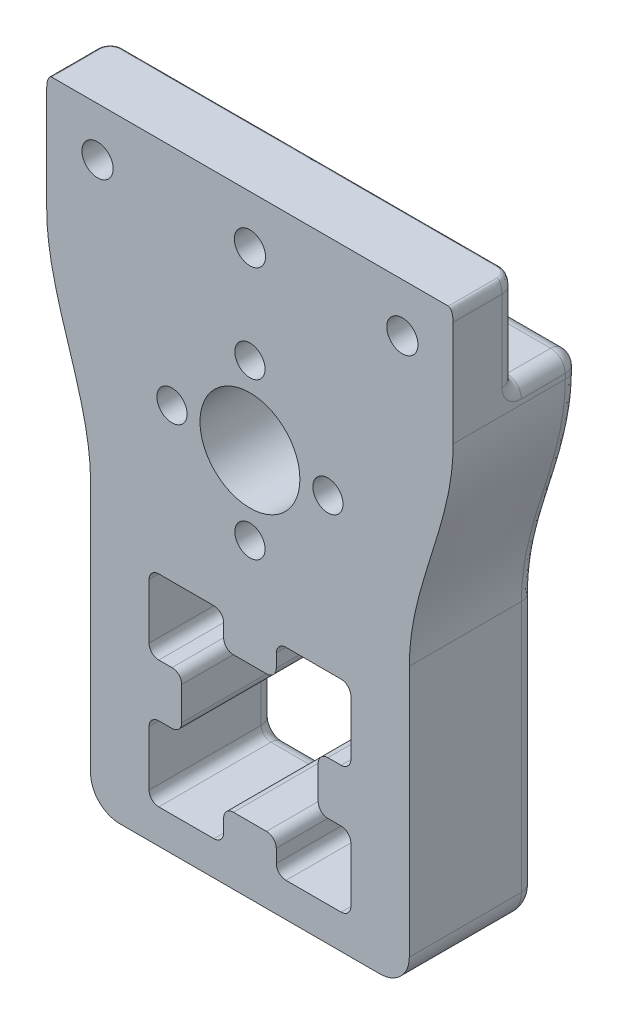
SolidWorks part; units mm, degrees
ref_plane "Alzado" through (0, 0, 0) normal (0, 0, 1) x (1, 0, 0)
ref_plane "Planta" through (0, 0, 0) normal (0, 1, 0) x (1, 0, 0)
ref_plane "Vista lateral" through (0, 0, 0) normal (1, 0, 0) x (0, 0, -1)
sketch "Croquis1" plane through (0, 0, 0) normal (0, 0, 1) x (1, 0, 0)
  line L1 (-10, 10) -> (10, 10) construction
  line L2 (-10, 10) -> (-10, -10) construction
  line L3 (-10, -10) -> (10, -10) construction
  line L4 (10, 10) -> (10, -10) construction
  line L5 (0, -10) -> (0, 10) construction
  line L6 (-10, 0) -> (10, 0) construction
  line L7 (10.35, -10.35) -> (-10.35, -10.35)
  line L8 (10.35, -10.35) -> (10.35, 10.35)
  line L9 (10.35, 10.35) -> (-10.35, 10.35)
  line L10 (-10.35, -10.35) -> (-10.35, 10.35)
  line L11 (0, 10.35) -> (0, -10.35) construction
  line L12 (10.35, 0) -> (-10.35, 0) construction
  point P0 (0, 0)
  point P4 (0, 0)
  dimension "D1" = 20
  dimension "D2" = 20
  dimension "D3" = 0.35
  dimension "D4" = 0.35
sketch "Croquis2" plane through (0, 0, 0) normal (0, 0, 1) x (1, 0, 0)
  line L0 (-7, -2.7) -> (-7, 2.7)
  line L1 (-10, -10) -> (10, -10) construction
  line L2 (-10, -10) -> (-10, 10) construction
  line L3 (-10, 10) -> (10, 10) construction
  line L4 (10, -10) -> (10, 10) construction
  line L5 (0, 10) -> (0, -10) construction
  line L6 (-10, 0) -> (10, 0) construction
  line L7 (-7, 2.7) -> (-10.35, 2.7)
  line L8 (-10.35, 2.7) -> (-10.35, 10.35)
  line L9 (-10.35, 10.35) -> (-2.7, 10.35)
  line L10 (-2.7, 10.35) -> (-2.7, 7)
  line L11 (-2.7, 7) -> (0, 7)
  line L12 (0, 10) -> (0, 26) construction
  line L13 (-22.5, 15) -> (28.9412, 15) construction
  line L14 (-22.5, 37) -> (43.6633, 37) construction
  line L15 (0, 26) -> (0, 47) construction
  line L16 (-22.5, 52) -> (22.5, 52) construction
  line L17 (-22.5, 52) -> (-22.5, 42) construction
  line L18 (-22.5, 42) -> (22.5, 42) construction
  line L19 (22.5, 52) -> (22.5, 42) construction
  line L20 (0, 42) -> (0, 52) construction
  line L21 (-22.5, 47) -> (22.5, 47) construction
  line L22 (-10.35, 10.35) -> (-10, 10) construction
  line L23 (-10, 10) -> (-10, 10.35) construction
  line L24 (-10, 0) -> (-67.4583, 0) construction
  line L25 (-16.35, 0) -> (-16.35, 15)
  line L26 (-20.85, 37) -> (-20.85, 39)
  line L27 (-20.85, 39) -> (0, 39)
  line L28 (-2.7, -7) -> (0, -7)
  line L29 (-2.7, -10.35) -> (-2.7, -7)
  line L30 (-10.35, -10.35) -> (-2.7, -10.35)
  line L31 (-10.35, -2.7) -> (-10.35, -10.35)
  line L32 (-7, -2.7) -> (-10.35, -2.7)
  line L33 (0, -10) -> (0, -13.85) construction
  line L34 (0, -13.85) -> (-16.35, -13.85)
  line L35 (-16.35, -13.85) -> (-16.35, 0)
  line L36 (0, -7) -> (0, -13.85)
  line L37 (0, 7) -> (0, 20.875)
  line L38 (0, 39) -> (0, 31.125)
  circle A0 centre (0, 26) radius 5.125 construction
  circle A1 centre (0, 26) radius 11 construction
  arc A2 (0, 31.125) -> (0, 20.875) centre (0, 26) ccw
  spline S0 degree 3 poles (-16.35, 15) (-16.35, 22.6413) (-20.85, 29.3331) (-20.85, 37) knots 0 0 0 0 1 1 1 1
  point P0 (0, 0)
  point P45 (-7, 0)
  point P104 (0, 47)
  dimension "D7" = 10.25
  dimension "D8" = 22
  dimension "D1" = 20
  dimension "D2" = 20
  dimension "D3" = 2.7
  dimension "D4" = 2.7
  dimension "D6" = 0.35
  dimension "D9" = 5
  dimension "D10" = 45
  dimension "D11" = 10
  dimension "D12" = 5
  dimension "D13" = 3
  dimension "D14" = 3
  dimension "D5" = 0.35
  dimension "D15" = 45
  dimension "D16" = 6
  dimension "D17" = 4.5
  dimension "D18" = 7.5
  dimension "D19" = 5.5
  dimension "D20" = 2
  dimension "D21" = 3.5
extrude "Saliente-Extruir1" add sketch "Croquis2" against normal blind 13 contours S0 L26 L27 L38 A2 L37 L11 L10 L9 L8 L7 L0 L32 L31 L30 L29 L28 L36 L34 L35 L25
sketch "Croquis3" plane through (0, 0, -13) normal (0, 0, -1) x (-1, 0, 0)
  line L0 (0, 26) -> (8, 26) construction
  circle A0 centre (0, 18) radius 1.55
  circle A1 centre (-8, 26) radius 1.55
  circle A2 centre (0, 26) radius 8 construction
  circle A4 centre (0, 26) radius 11.25
  circle A5 centre (0, 26) radius 11.25
  circle A6 centre (8, 26) radius 1.55
  circle A7 centre (0, 34) radius 1.55
  point P15 (0, 26)
  line M11 (0, 39) -> (0, 31.125)
  arc M12 (0, 31.125) -> (0, 20.875) centre (0, 26) cw
  line M13 (0, 20.875) -> (0, 7)
  dimension "D2" = 16
  dimension "D3" = 3.1
  dimension "D1" = 0.25
  dimension "D4" = 4
extrude "Saliente-Extruir2" add sketch "Croquis3" against normal blind 5.5 contours A6 | A7 M11 | A7 A0 A5 A6 M11 M12 M13 | A0 M13 region at (-0.6578, 18, -13) region at (-5.5748, 26, -13) region at (-0.6578, 34, -13) region at (-8, 26, -13)
extrude "Cortar-Extruir1" cut sketch "Croquis3<3>" against normal blind 4 contours A5
sketch "Croquis3<3>" plane through (0, 0, -13) normal (0, 0, -1) x (-1, 0, 0) same geometry as "Croquis3"
extrude "Cortar-Extruir2" cut sketch "Croquis3<4>" against normal through all contours A7 | A0 | A6
sketch "Croquis3<4>" plane through (0, 0, -13) normal (0, 0, -1) x (-1, 0, 0) same geometry as "Croquis3"
sketch "Croquis4" plane through (-20.85, 0, 0) normal (-1, 0, 0) x (0, 0, 1)
  line L0 (0, 39) -> (-13, 39) construction
  line L1 (0, 39) -> (-6.5, 39)
  line L2 (0, 39) -> (0, 45)
  line L3 (0, 45) -> (-6.5, 45)
  line L4 (-6.5, 39) -> (-6.5, 45)
  line L5 (-3.25, 45) -> (-3.25, 39) construction
  line L6 (0, 42) -> (-6.5, 42) construction
  point P80 (-3.25, 42)
  dimension "D1" = 6
extrude "Saliente-Extruir3" add sketch "Croquis4" against normal up to surface (20.85 mm away) up to face at (0, 37.2667, -7.3333)
sketch "Croquis5" plane through (0, 0, 0) normal (1, 0, 0) x (0, 0, -1)
  line L0 (13, 39) -> (13, -13.85) construction
  line L1 (19.806, 39) -> (13, 39)
  line L2 (13, 25.4907) -> (13, 39)
  spline S0 degree 3 poles (13, 25.4907) (13, 27.6441) (13.5424, 32.3804) (16.2938, 36.9604) (18.5325, 39) (19.806, 39) knots 0 0 0 0 0.453183 0.799124 1 1 1 1
fillet "Redondeo2" radius 1.5 1 edges at (-10.425, 39, -13)
fillet "Redondeo3" radius 1 1 edges at (-11.25, 26, -13)
fillet "Redondeo4" radius 1 1 edges at (-11.25, 26, -9)
fillet "Redondeo5" radius 0.5 1 edges at (-10.425, 39, -6.5)
fillet "Redondeo6" radius 3 1 edges at (-16.35, -13.85, -6.5)
sketch "Croquis7" plane through (0, 0, 0) normal (0, 0, 1) x (1, 0, 0)
  line L1 (0, 45) -> (-20.85, 45)
  line L2 (0, 45) -> (0, 49)
  line L3 (0, 49) -> (-20.85, 49)
  line L4 (-20.85, 45) -> (-20.85, 49)
  line L5 (-10.425, 49) -> (-10.425, 45) construction
  line L6 (0, 47) -> (-20.85, 47) construction
  line L7 (-20.85, 37) -> (-20.85, 45) construction
  line L8 (-22.5, 52) -> (22.5, 52) construction
  point P128 (-10.425, 47)
  dimension "D1" = 3
extrude "Saliente-Extruir6" add sketch "Croquis7" against normal up to surface (6.5 mm away) up to face at (-10.425, 42.25, -6.5)
sketch "Croquis8" plane through (0, 0, -6.5) normal (0, 0, -1) x (-1, 0, 0)
  line L0 (20.85, 39) -> (0, 39) construction
  line L1 (0, 49) -> (20.85, 49) construction
  line L2 (0, 49) -> (0, 39) construction
  line L3 (0, 39) -> (20.85, 39) construction
  line L4 (20.85, 49) -> (20.85, 39) construction
  line L5 (10.425, 39) -> (10.425, 49) construction
  line L6 (0, 44) -> (20.85, 44) construction
  line L7 (20.85, 49) -> (20.85, 39.5) construction
  line L8 (10.425, 44) -> (20.85, 44) construction
  circle A0 centre (0, 44) radius 1.6
  circle A1 centre (15.6375, 44) radius 1.6
  point P140 (10.425, 44)
  dimension "D1" = 3.2
  dimension "D2" = 3.2
extrude "Cortar-Extruir4" cut sketch "Croquis8" against normal through all
fillet "Redondeo7" radius 1 10 edges at (-2.7, -7, -6.5) (-2.7, -10.35, -6.5) (-10.35, -10.35, -6.5) (-10.35, -2.7, -6.5) (-7, -2.7, -6.5) (-7, 2.7, -6.5) (-10.35, 2.7, -6.5) (-10.35, 10.35, -6.5) (-2.7, 10.35, -6.5) (-2.7, 7, -6.5)
fillet "Redondeo8" radius 1.5 9 edges at (-20.85, 44.25, -6.5) (-20.85, 39.1464, -6.6464) (-20.85, 39, -9.25) (-20.85, 38.5607, -12.5607) (-20.85, 37.25, -13) (-16.35, 2.075, -13) (-15.4713, -12.9713, -13) (-6.675, -13.85, -13)
fillet "Redondeo9" radius 1.5 21 edges at (-0.85, 7, -13) (-2.4071, 7.2929, -13) (-2.7, 8.675, -13) (-2.9929, 10.0571, -13) (-6.525, 10.35, -13) (-10.0571, 10.0571, -13) (-10.35, 6.525, -13) (-10.0571, 2.9929, -13) (-8.675, 2.7, -13) (-7.2929, 2.4071, -13) (-7, 0, -13) (-7.2929, -2.4071, -13) (-8.675, -2.7, -13) (-10.0571, -2.9929, -13) (-10.35, -6.525, -13) (-10.0571, -10.0571, -13) (-6.525, -10.35, -13) (-2.9929, -10.0571, -13) (-2.7, -8.675, -13) (-2.4071, -7.2929, -13) (-0.85, -7, -13)
fillet "Redondeo11" radius 1.2 3 edges at (-20.85, 49, -2.5) (-20.4107, 49, -6.0607) (-9.675, 49, -6.5) second distance 0.5 first distance on face at (-20.85, 40.8694, -5.6551) first distance on face at (-20.2553, 44.25, -5.9053) first distance on face at (-6.7167, 44.1667, -6.5)
mirror "Simetría1" about plane through (0, 0, 0) normal (1, 0, 0) of bodies 110 105
ref_plane "Plano1" through (0, 0, 0) normal (0, -1, 0) x (-1, 0, 0)
ref_plane "Plano2" through (0, 0, 0) normal (-1, 0, 0) x (0, 0, 1)
equation "\"tolerancia\" = 0.35"
equation "\"D5@Croquis2\"=\"tolerancia\""
equation "\"D6@Croquis2\"=\"tolerancia\""
equation "\"D3@Croquis2\"=(6.10/2)-\"tolerancia\""
equation "\"D4@Croquis2\"=(6.10/2) - \"tolerancia\""
